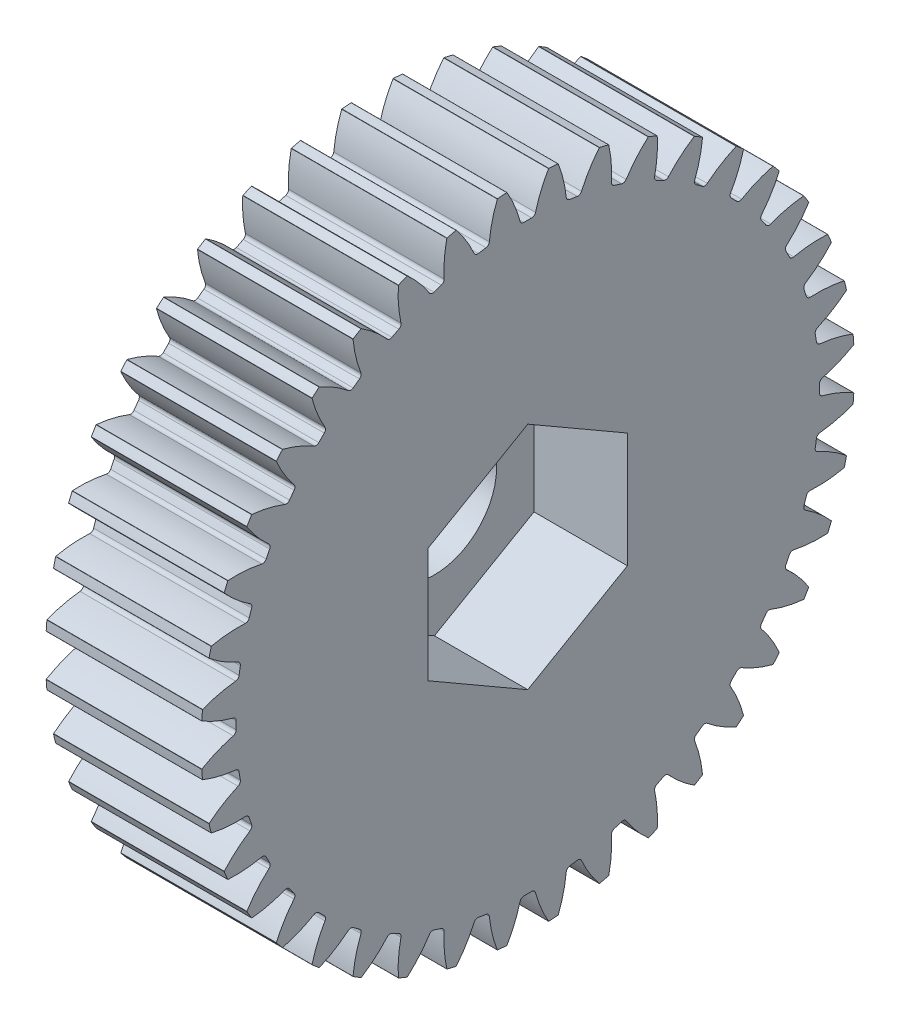
SolidWorks part; units mm, degrees
ref_plane "Plane1" through (0, 0, 0) normal (0, 0, 1) x (1, 0, 0)
ref_plane "Plane2" through (0, 0, 0) normal (0, 1, 0) x (1, 0, 0)
ref_plane "Plane3" through (0, 0, 0) normal (1, 0, 0) x (0, 0, -1)
sketch "HoldingSke" plane through (0, 0, 0) normal (0, 1, 0) x (1, 0, 0)
  line L0 (0, 0) -> (0.766, -0.6428)
  line L1 (-15, 0) -> (100, 0) construction
  line L2 (0, 0) -> (-2.1039, 2.3779)
  line L3 (0, 0) -> (-11.863, 4.5341)
  line L4 (0, 0) -> (6.6156, 5.5511)
  line L5 (0, 0) -> (-46.8476, -17.4728)
  line L6 (0, 0) -> (-11.6055, -7.8303)
  line L7 (-2.1039, 2.3779) -> (8.6586, 51.2059)
  line L8 (-76.2, 54.61) -> (-75.5, 54.61)
  line L9 (-71.009, 38.7566) -> (-53.1078, 45.2721)
  line L10 (-76.2, 71.12) -> (104.1128, 71.12)
  line L11 (0, 0) -> (-14, 0)
  line L12 (-76.2, 101.6) -> (-76.162, 101.6)
  line L13 (24.9733, 27.94) -> (52.9518, 28.4284)
  line L14 (24.9733, 27.94) -> (24.9743, 27.94)
  line L15 (24.9733, 27.94) -> (100.4006, 29.5858)
  line L16 (-63.627, -1) -> (-12.827, -1)
  circle A0 centre (0, 0) radius 2
  circle A1 centre (0, 0) radius 18.749
  circle A2 centre (0, 0) radius 37.5
  circle A3 centre (0, 0) radius 2
  dimension "MHD" = 37.498
  dimension "Hub_dia" = 75
  dimension "Bore" = 4
  dimension "MBD" = 4
  dimension "Num_teeth" = 40
  dimension "Pitch" = 1
  dimension "Overall_len" = 50
  dimension "Show_teeth" = 40
  dimension "Thickness" = 14
  dimension "OAL" = 50.0001
  dimension "T_dim" = 0.7
  dimension "Ap" = 20
  dimension "H" = 19.05
  dimension "Pitch_radius" = 180.3128
  dimension "Width" = 14
  dimension "Backlash" = 0.038
  dimension "Addendum_fac" = 1
  dimension "Dedendum_fac" = 1.25
  dimension "Clearance_fac" = 0.25
  dimension "Dedendum_add" = 0.001
  dimension "Module" = 1
sketch "BasProSke" plane through (0, 0, 0) normal (0, 1, 0) x (1, 0, 0)
  line L0 (-10, 0) -> (60, 0) construction
  line L1 (0, 0) -> (0, 21)
  line L2 (0, 0) -> (14, 0)
  line L3 (14, 0) -> (14, 21)
  line L4 (14, 21) -> (0, 21)
  dimension "Thickness" = 14
  dimension "Diameter" = 42
revolve "Base-Revolve" add sketch "BasProSke" angle 360 about L0
sketch "TooCutSke" plane through (0, 0, 0) normal (1, 0, 0) x (0, 0, -1)
  line L1 (0, 0) -> (0, 107) construction
  line L2 (0, 0) -> (-0.8517, 19.9819) construction
  line L3 (0, 0) -> (-3.1363, 39.8509) construction
  line L4 (-0.8517, 19.9819) -> (-1.5682, 19.9255) construction
  arc A0 (0.4487, 18.7436) -> (-0.4487, 18.7436) centre (0, 0) ccw
  arc A1 (1.3547, 20.9817) -> (-1.3547, 20.9817) centre (0, 0) ccw
  circle A2 centre (0, 0) radius 20 construction
  circle A3 centre (0, 0) radius 18.7939 construction
  arc A4 (-0.4487, 18.7436) -> (-1.3547, 20.9817) centre (-8.2322, 16.895) ccw
  arc A5 (1.3547, 20.9817) -> (0.4487, 18.7436) centre (8.2322, 16.895) ccw
  dimension "Root_dia" = 37.498
  dimension "Overcut_dia" = 42.0508
  dimension "Pitch_dia" = 40
  dimension "Base_dia" = 37.5877
  dimension "Flank_rad" = 8
  dimension "Half_ang" = 4.5
  dimension "Half_CT" = 0.7187
extrude "ToothCut" cut sketch "TooCutSke" along normal through all
fillet "Breaks" radius 0.02 2 edges at (7, 20.9572, -1.3402) (7, 20.9572, 1.3402) tangent propagation no
fillet "RootFillets" radius 0.251 2 edges at (7, 18.7436, -0.4487) (7, 18.7436, 0.4487)
pattern_circular "TeethCuts" count 40 every 9 about axis through (-10, 0, 0) along (1, 0, 0) of "ToothCut", "RootFillets", "Breaks"
sketch "HubNeaOneSke" plane through (0, 0, 0) normal (-1, 0, 0) x (0, 0, 1)
  circle A0 centre (0, 0) radius 18.749
  dimension "Diameter" = 37.498
extrude "HubNearOne" [suppressed] add sketch "HubNeaOneSke" along normal blind 36.0001
sketch "HubNeaBotSke" plane through (0, 0, 0) normal (-1, 0, 0) x (0, 0, 1)
  circle A0 centre (0, 0) radius 18.749
  dimension "Diameter" = 37.498
extrude "HubNearBoth" [suppressed] add sketch "HubNeaBotSke" along normal blind 18
ref_plane "FarPln" through (14, 0, 0) normal (1, 0, 0) x (0, 0, -1)
sketch "HubFarSke" plane through (14, 0, 0) normal (1, 0, 0) x (0, 0, -1)
  circle A0 centre (0, 0) radius 18.749
  dimension "Diameter" = 37.498
extrude "HubFar" [suppressed] add sketch "HubFarSke" along normal blind 18
sketch "BorSke" plane through (0, 0, 0) normal (1, 0, 0) x (0, 0, -1)
  circle A0 centre (0, 0) radius 2
extrude "Bore" cut sketch "BorSke" along normal mid plane 100.0001
sketch "KeySke" plane through (0, 0, 0) normal (1, 0, 0) x (0, 0, -1)
  line L0 (-0.8, 0) -> (-0.8, 2.7)
  line L1 (-0.8, 2.7) -> (0.8, 2.7)
  line L2 (0.8, 2.7) -> (0.8, 0)
  line L3 (0, 0) -> (0, 34) construction
  line L4 (-0.8, 0) -> (0.8, 0)
  dimension "Offset" = 2.7
  dimension "Width" = 1.6
extrude "Keyway" [suppressed] cut sketch "KeySke" along normal mid plane 100.0001
pattern_circular "Keyway2" [suppressed] count 2 every 90 about axis through (-10, 0, 0) along (1, 0, 0)
sketch "Sketch1" plane through (14, 0, 0) normal (1, 0, 0) x (0, 0, -1)
  line L1 (0, 7.3901) -> (-6.4, 3.695)
  line L2 (-6.4, 3.695) -> (-6.4, -3.695)
  line L3 (-6.4, -3.695) -> (0, -7.3901)
  line L4 (0, -7.3901) -> (6.4, -3.695)
  line L5 (6.4, -3.695) -> (6.4, 3.695)
  line L6 (6.4, 3.695) -> (0, 7.3901)
  circle A0 centre (0, 0) radius 7.3901
  circle A2 centre (0, 0) radius 6.4 construction
  circle A3 centre (0, 0) radius 4
  dimension "D1" = 8
  dimension "D2" = 12.8
extrude "Cut-Extrude1" cut sketch "Sketch1" against normal blind 6 contours L1 L2 L3 L4 L5 L6
extrude "Cut-Extrude2" cut sketch "Sketch1<7>" against normal through all contours A3 region at (14, 0, 0)
sketch "Sketch1<7>" plane through (14, 0, 0) normal (1, 0, 0) x (0, 0, -1) same geometry as "Sketch1"
sketch "Sketch2" plane through (0, 0, 0) normal (-1, 0, 0) x (0, 0, 1)
  circle A0 centre (0, 0) radius 6.5
  circle A1 centre (0, 0) radius 4
  dimension "D1" = 13
  dimension "D2" = 8
extrude "Boss-Extrude1" add sketch "Sketch2" along normal blind 3.8
sketch "Sketch3" plane through (8, 0, 0) normal (1, 0, 0) x (0, 0, -1)
  line L1 (4, 4) -> (-4, 4)
  line L2 (4, 4) -> (4, -4)
  line L3 (4, -4) -> (-4, -4)
  line L4 (-4, 4) -> (-4, -4)
  line L6 (5.5, 5.5) -> (5.5, -5.5)
  line L7 (5.5, -5.5) -> (-5.5, -5.5)
  line L8 (-5.5, 5.5) -> (-5.5, -5.5)
  line L9 (5.5, 5.5) -> (-5.5, 5.5)
  line L10 (5.5, 4) -> (5.8718, 4)
  line L11 (6.4, 3.695) -> (0, 7.3901) construction
  line L12 (5.5, -4) -> (5.8718, -4)
  line L13 (0, -7.3901) -> (6.4, -3.695) construction
  line L14 (-5.5, -4) -> (-5.8718, -4)
  line L15 (-6.4, -3.695) -> (0, -7.3901) construction
  line L16 (-5.5, 4) -> (-5.8718, 4)
  line L17 (0, 7.3901) -> (-6.4, 3.695) construction
  circle A0 centre (0, 0) radius 4 construction
  line M10 (6.4, 3.695) -> (0, 7.3901)
  line M11 (0, 7.3901) -> (-6.4, 3.695)
  line M13 (-6.4, -3.695) -> (0, -7.3901)
  line M14 (0, -7.3901) -> (6.4, -3.695)
  dimension "D1" = 1.5
extrude "Boss-Extrude2" [suppressed] add sketch "Sketch3" along normal blind 0.3 contours L9 L8 L7 L6 L4 L1 L2 L3 M10 M11 M13 M14 | L12 L6 M14 | L6 L10 M10 | L16 L8 M11 | L8 L14 M13
sketch "Sketch4" plane through (0, 0, 0) normal (-1, 0, 0) x (0, 0, 1)
  circle A324 centre (0, 0) radius 6.5
  circle A325 centre (0, 0) radius 6.5
  arc A644 (-2.6854, 18.5557) -> (-3.18, 18.4773) centre (0, 0) ccw
  arc A645 (-3.4523, 18.6235) -> (-3.18, 18.4773) centre (-3.2226, 18.7247) ccw
  arc A646 (-3.4523, 18.6235) -> (-4.5943, 20.48) centre (-10.7738, 15.3992) ccw
  arc A647 (-4.5943, 20.48) -> (-4.6142, 20.4868) centre (-4.6098, 20.4673) ccw
  arc A648 (-4.6142, 20.4868) -> (-5.1896, 20.3487) centre (0, 0) ccw
  arc A649 (-5.1896, 20.3487) -> (-5.2042, 20.3336) centre (-5.1846, 20.3293) ccw
  arc A650 (-5.2042, 20.3336) -> (-5.3789, 18.161) centre (2.6084, 18.612) ccw
  arc A651 (-5.5551, 17.9071) -> (-5.3789, 18.161) centre (-5.6295, 18.1469) ccw
  arc A652 (-5.5551, 17.9071) -> (-6.0314, 17.7524) centre (0, 0) ccw
  arc A653 (-6.3232, 17.8542) -> (-6.0314, 17.7524) centre (-6.1121, 17.9901) ccw
  arc A654 (-6.3232, 17.8542) -> (-7.7415, 19.5091) centre (-13.0501, 13.5242) ccw
  arc A655 (-7.7415, 19.5091) -> (-7.7622, 19.5128) centre (-7.7548, 19.4942) ccw
  arc A656 (-7.7622, 19.5128) -> (-8.3089, 19.2863) centre (0, 0) ccw
  arc A657 (-8.3089, 19.2863) -> (-8.321, 19.2691) centre (-8.301, 19.268) ccw
  arc A658 (-8.321, 19.2691) -> (-8.1537, 17.096) centre (-0.3353, 18.7909) ccw
  arc A659 (-8.288, 16.8177) -> (-8.1537, 17.096) centre (-8.399, 17.0428) ccw
  arc A660 (-8.288, 16.8177) -> (-8.7342, 16.5903) centre (0, 0) ccw
  arc A661 (-9.0383, 16.6452) -> (-8.7342, 16.5903) centre (-8.8511, 16.8124) ccw
  arc A662 (-9.0383, 16.6452) -> (-10.6981, 18.0579) centre (-15.0051, 11.3162) ccw
  arc A663 (-10.6981, 18.0579) -> (-10.7191, 18.0583) centre (-10.7089, 18.0411) ccw
  arc A664 (-10.7191, 18.0583) -> (-11.2237, 17.7491) centre (0, 0) ccw
  arc A665 (-11.2237, 17.7491) -> (-11.2329, 17.7302) centre (-11.213, 17.7322) ccw
  arc A666 (-11.2329, 17.7302) -> (-10.7277, 15.61) centre (-3.2707, 18.5071) ccw
  arc A667 (-10.8168, 15.3141) -> (-10.7277, 15.61) centre (-10.9616, 15.5191) ccw
  arc A668 (-10.8168, 15.3141) -> (-11.222, 15.0197) centre (0, 0) ccw
  arc A669 (-11.5309, 15.0264) -> (-11.222, 15.0197) centre (-11.3722, 15.2208) ccw
  arc A670 (-11.5309, 15.0264) -> (-13.3913, 16.162) centre (-16.5906, 8.8296) ccw
  arc A671 (-13.3913, 16.162) -> (-13.4121, 16.1591) centre (-13.3993, 16.1437) ccw
  arc A672 (-13.4121, 16.1591) -> (-13.862, 15.7748) centre (0, 0) ccw
  arc A673 (-13.862, 15.7748) -> (-13.8682, 15.7547) centre (-13.8488, 15.7598) ccw
  arc A674 (-13.8682, 15.7547) -> (-13.0375, 13.7396) centre (-6.1256, 17.7676) ccw
  arc A675 (-13.0793, 13.4334) -> (-13.0375, 13.7396) centre (-13.2544, 13.6133) ccw
  arc A676 (-13.0793, 13.4334) -> (-13.4334, 13.0793) centre (0, 0) ccw
  arc A677 (-13.7396, 13.0375) -> (-13.4334, 13.0793) centre (-13.6133, 13.2544) ccw
  arc A678 (-13.7396, 13.0375) -> (-15.7547, 13.8682) centre (-17.7676, 6.1256) ccw
  arc A679 (-15.7547, 13.8682) -> (-15.7748, 13.862) centre (-15.7598, 13.8488) ccw
  arc A680 (-15.7748, 13.862) -> (-16.1591, 13.4121) centre (0, 0) ccw
  arc A681 (-16.1591, 13.4121) -> (-16.162, 13.3913) centre (-16.1437, 13.3993) ccw
  arc A682 (-16.162, 13.3913) -> (-15.0264, 11.5309) centre (-8.8296, 16.5906) ccw
  arc A683 (-15.0197, 11.222) -> (-15.0264, 11.5309) centre (-15.2208, 11.3722) ccw
  arc A684 (-15.0197, 11.222) -> (-15.3141, 10.8168) centre (0, 0) ccw
  arc A685 (-15.61, 10.7277) -> (-15.3141, 10.8168) centre (-15.5191, 10.9616) ccw
  arc A686 (-15.61, 10.7277) -> (-17.7302, 11.2329) centre (-18.5071, 3.2707) ccw
  arc A687 (-17.7302, 11.2329) -> (-17.7491, 11.2237) centre (-17.7322, 11.213) ccw
  arc A688 (-17.7491, 11.2237) -> (-18.0583, 10.7191) centre (0, 0) ccw
  arc A689 (-18.0583, 10.7191) -> (-18.0579, 10.6981) centre (-18.0411, 10.7089) ccw
  arc A690 (-18.0579, 10.6981) -> (-16.6452, 9.0383) centre (-11.3162, 15.0051) ccw
  arc A691 (-16.5903, 8.7342) -> (-16.6452, 9.0383) centre (-16.8124, 8.8511) ccw
  arc A692 (-16.5903, 8.7342) -> (-16.8177, 8.288) centre (0, 0) ccw
  arc A693 (-17.096, 8.1537) -> (-16.8177, 8.288) centre (-17.0428, 8.399) ccw
  arc A694 (-17.096, 8.1537) -> (-19.2691, 8.321) centre (-18.7909, 0.3353) ccw
  arc A695 (-19.2691, 8.321) -> (-19.2863, 8.3089) centre (-19.268, 8.301) ccw
  arc A696 (-19.2863, 8.3089) -> (-19.5128, 7.7622) centre (0, 0) ccw
  arc A697 (-19.5128, 7.7622) -> (-19.5091, 7.7415) centre (-19.4942, 7.7548) ccw
  arc A698 (-19.5091, 7.7415) -> (-17.8542, 6.3232) centre (-13.5242, 13.0501) ccw
  arc A699 (-17.7524, 6.0314) -> (-17.8542, 6.3232) centre (-17.9901, 6.1121) ccw
  arc A700 (-17.7524, 6.0314) -> (-17.9071, 5.5551) centre (0, 0) ccw
  arc A701 (-18.161, 5.3789) -> (-17.9071, 5.5551) centre (-18.1469, 5.6295) ccw
  arc A702 (-18.161, 5.3789) -> (-20.3336, 5.2042) centre (-18.612, -2.6084) ccw
  arc A703 (-20.3336, 5.2042) -> (-20.3487, 5.1896) centre (-20.3293, 5.1846) ccw
  arc A704 (-20.3487, 5.1896) -> (-20.4868, 4.6142) centre (0, 0) ccw
  arc A705 (-20.4868, 4.6142) -> (-20.48, 4.5943) centre (-20.4673, 4.6098) ccw
  arc A706 (-20.48, 4.5943) -> (-18.6235, 3.4523) centre (-15.3992, 10.7738) ccw
  arc A707 (-18.4773, 3.18) -> (-18.6235, 3.4523) centre (-18.7247, 3.2226) ccw
  arc A708 (-18.4773, 3.18) -> (-18.5557, 2.6854) centre (0, 0) ccw
  arc A709 (-18.7789, 2.4716) -> (-18.5557, 2.6854) centre (-18.8041, 2.7214) ccw
  arc A710 (-18.7789, 2.4716) -> (-20.8974, 1.9592) centre (-17.9748, -5.4878) ccw
  arc A711 (-20.8974, 1.9592) -> (-20.91, 1.9424) centre (-20.8901, 1.9406) ccw
  arc A712 (-20.91, 1.9424) -> (-20.9564, 1.3525) centre (0, 0) ccw
  arc A713 (-20.9564, 1.3525) -> (-20.9466, 1.334) centre (-20.9364, 1.3512) ccw
  arc A714 (-20.9466, 1.334) -> (-18.9343, 0.4964) centre (-16.895, 8.2322) ccw
  arc A715 (-18.7473, 0.2504) -> (-18.9343, 0.4964) centre (-18.9983, 0.2537) ccw
  arc A716 (-18.7473, 0.2504) -> (-18.7473, -0.2504) centre (0, 0) ccw
  arc A717 (-18.9343, -0.4964) -> (-18.7473, -0.2504) centre (-18.9983, -0.2537) ccw
  arc A718 (-18.9343, -0.4964) -> (-20.9466, -1.334) centre (-16.895, -8.2322) ccw
  arc A719 (-20.9466, -1.334) -> (-20.9564, -1.3525) centre (-20.9364, -1.3512) ccw
  arc A720 (-20.9564, -1.3525) -> (-20.91, -1.9424) centre (0, 0) ccw
  arc A721 (-20.91, -1.9424) -> (-20.8974, -1.9592) centre (-20.8901, -1.9406) ccw
  arc A722 (-20.8974, -1.9592) -> (-18.7789, -2.4716) centre (-17.9748, 5.4878) ccw
  arc A723 (-18.5557, -2.6854) -> (-18.7789, -2.4716) centre (-18.8041, -2.7214) ccw
  arc A724 (-18.5557, -2.6854) -> (-18.4773, -3.18) centre (0, 0) ccw
  arc A725 (-18.6235, -3.4523) -> (-18.4773, -3.18) centre (-18.7247, -3.2226) ccw
  arc A726 (-18.6235, -3.4523) -> (-20.48, -4.5943) centre (-15.3992, -10.7738) ccw
  arc A727 (-20.48, -4.5943) -> (-20.4868, -4.6142) centre (-20.4673, -4.6098) ccw
  arc A728 (-20.4868, -4.6142) -> (-20.3487, -5.1896) centre (0, 0) ccw
  arc A729 (-20.3487, -5.1896) -> (-20.3336, -5.2042) centre (-20.3293, -5.1846) ccw
  arc A730 (-20.3336, -5.2042) -> (-18.161, -5.3789) centre (-18.612, 2.6084) ccw
  arc A731 (-17.9071, -5.5551) -> (-18.161, -5.3789) centre (-18.1469, -5.6295) ccw
  arc A732 (-17.9071, -5.5551) -> (-17.7524, -6.0314) centre (0, 0) ccw
  arc A733 (-17.8542, -6.3232) -> (-17.7524, -6.0314) centre (-17.9901, -6.1121) ccw
  arc A734 (-17.8542, -6.3232) -> (-19.5091, -7.7415) centre (-13.5242, -13.0501) ccw
  arc A735 (-19.5091, -7.7415) -> (-19.5128, -7.7622) centre (-19.4942, -7.7548) ccw
  arc A736 (-19.5128, -7.7622) -> (-19.2863, -8.3089) centre (0, 0) ccw
  arc A737 (-19.2863, -8.3089) -> (-19.2691, -8.321) centre (-19.268, -8.301) ccw
  arc A738 (-19.2691, -8.321) -> (-17.096, -8.1537) centre (-18.7909, -0.3353) ccw
  arc A739 (-16.8177, -8.288) -> (-17.096, -8.1537) centre (-17.0428, -8.399) ccw
  arc A740 (-16.8177, -8.288) -> (-16.5903, -8.7342) centre (0, 0) ccw
  arc A741 (-16.6452, -9.0383) -> (-16.5903, -8.7342) centre (-16.8124, -8.8511) ccw
  arc A742 (-16.6452, -9.0383) -> (-18.0579, -10.6981) centre (-11.3162, -15.0051) ccw
  arc A743 (-18.0579, -10.6981) -> (-18.0583, -10.7191) centre (-18.0411, -10.7089) ccw
  arc A744 (-18.0583, -10.7191) -> (-17.7491, -11.2237) centre (0, 0) ccw
  arc A745 (-17.7491, -11.2237) -> (-17.7302, -11.2329) centre (-17.7322, -11.213) ccw
  arc A746 (-17.7302, -11.2329) -> (-15.61, -10.7277) centre (-18.5071, -3.2707) ccw
  arc A747 (-15.3141, -10.8168) -> (-15.61, -10.7277) centre (-15.5191, -10.9616) ccw
  arc A748 (-15.3141, -10.8168) -> (-15.0197, -11.222) centre (0, 0) ccw
  arc A749 (-15.0264, -11.5309) -> (-15.0197, -11.222) centre (-15.2208, -11.3722) ccw
  arc A750 (-15.0264, -11.5309) -> (-16.162, -13.3913) centre (-8.8296, -16.5906) ccw
  arc A751 (-16.162, -13.3913) -> (-16.1591, -13.4121) centre (-16.1437, -13.3993) ccw
  arc A752 (-16.1591, -13.4121) -> (-15.7748, -13.862) centre (0, 0) ccw
  arc A753 (-15.7748, -13.862) -> (-15.7547, -13.8682) centre (-15.7598, -13.8488) ccw
  arc A754 (-15.7547, -13.8682) -> (-13.7396, -13.0375) centre (-17.7676, -6.1256) ccw
  arc A755 (-13.4334, -13.0793) -> (-13.7396, -13.0375) centre (-13.6133, -13.2544) ccw
  arc A756 (-13.4334, -13.0793) -> (-13.0793, -13.4334) centre (0, 0) ccw
  arc A757 (-13.0375, -13.7396) -> (-13.0793, -13.4334) centre (-13.2544, -13.6133) ccw
  arc A758 (-13.0375, -13.7396) -> (-13.8682, -15.7547) centre (-6.1256, -17.7676) ccw
  arc A759 (-13.8682, -15.7547) -> (-13.862, -15.7748) centre (-13.8488, -15.7598) ccw
  arc A760 (-13.862, -15.7748) -> (-13.4121, -16.1591) centre (0, 0) ccw
  arc A761 (-13.4121, -16.1591) -> (-13.3913, -16.162) centre (-13.3993, -16.1437) ccw
  arc A762 (-13.3913, -16.162) -> (-11.5309, -15.0264) centre (-16.5906, -8.8296) ccw
  arc A763 (-11.222, -15.0197) -> (-11.5309, -15.0264) centre (-11.3722, -15.2208) ccw
  arc A764 (-11.222, -15.0197) -> (-10.8168, -15.3141) centre (0, 0) ccw
  arc A765 (-10.7277, -15.61) -> (-10.8168, -15.3141) centre (-10.9616, -15.5191) ccw
  arc A766 (-10.7277, -15.61) -> (-11.2329, -17.7302) centre (-3.2707, -18.5071) ccw
  arc A767 (-11.2329, -17.7302) -> (-11.2237, -17.7491) centre (-11.213, -17.7322) ccw
  arc A768 (-11.2237, -17.7491) -> (-10.7191, -18.0583) centre (0, 0) ccw
  arc A769 (-10.7191, -18.0583) -> (-10.6981, -18.0579) centre (-10.7089, -18.0411) ccw
  arc A770 (-10.6981, -18.0579) -> (-9.0383, -16.6452) centre (-15.0051, -11.3162) ccw
  arc A771 (-8.7342, -16.5903) -> (-9.0383, -16.6452) centre (-8.8511, -16.8124) ccw
  arc A772 (-8.7342, -16.5903) -> (-8.288, -16.8177) centre (0, 0) ccw
  arc A773 (-8.1537, -17.096) -> (-8.288, -16.8177) centre (-8.399, -17.0428) ccw
  arc A774 (-8.1537, -17.096) -> (-8.321, -19.2691) centre (-0.3353, -18.7909) ccw
  arc A775 (-8.321, -19.2691) -> (-8.3089, -19.2863) centre (-8.301, -19.268) ccw
  arc A776 (-8.3089, -19.2863) -> (-7.7622, -19.5128) centre (0, 0) ccw
  arc A777 (-7.7622, -19.5128) -> (-7.7415, -19.5091) centre (-7.7548, -19.4942) ccw
  arc A778 (-7.7415, -19.5091) -> (-6.3232, -17.8542) centre (-13.0501, -13.5242) ccw
  arc A779 (-6.0314, -17.7524) -> (-6.3232, -17.8542) centre (-6.1121, -17.9901) ccw
  arc A780 (-6.0314, -17.7524) -> (-5.5551, -17.9071) centre (0, 0) ccw
  arc A781 (-5.3789, -18.161) -> (-5.5551, -17.9071) centre (-5.6295, -18.1469) ccw
  arc A782 (-5.3789, -18.161) -> (-5.2042, -20.3336) centre (2.6084, -18.612) ccw
  arc A783 (-5.2042, -20.3336) -> (-5.1896, -20.3487) centre (-5.1846, -20.3293) ccw
  arc A784 (-5.1896, -20.3487) -> (-4.6142, -20.4868) centre (0, 0) ccw
  arc A785 (-4.6142, -20.4868) -> (-4.5943, -20.48) centre (-4.6098, -20.4673) ccw
  arc A786 (-4.5943, -20.48) -> (-3.4523, -18.6235) centre (-10.7738, -15.3992) ccw
  arc A787 (-3.18, -18.4773) -> (-3.4523, -18.6235) centre (-3.2226, -18.7247) ccw
  arc A788 (-3.18, -18.4773) -> (-2.6854, -18.5557) centre (0, 0) ccw
  arc A789 (-2.4716, -18.7789) -> (-2.6854, -18.5557) centre (-2.7214, -18.8041) ccw
  arc A790 (-2.4716, -18.7789) -> (-1.9592, -20.8974) centre (5.4878, -17.9748) ccw
  arc A791 (-1.9592, -20.8974) -> (-1.9424, -20.91) centre (-1.9406, -20.8901) ccw
  arc A792 (-1.9424, -20.91) -> (-1.3525, -20.9564) centre (0, 0) ccw
  arc A793 (-1.3525, -20.9564) -> (-1.334, -20.9466) centre (-1.3512, -20.9364) ccw
  arc A794 (-1.334, -20.9466) -> (-0.4964, -18.9343) centre (-8.2322, -16.895) ccw
  arc A795 (-0.2504, -18.7473) -> (-0.4964, -18.9343) centre (-0.2537, -18.9983) ccw
  arc A796 (-0.2504, -18.7473) -> (0.2504, -18.7473) centre (0, 0) ccw
  arc A797 (0.4964, -18.9343) -> (0.2504, -18.7473) centre (0.2537, -18.9983) ccw
  arc A798 (0.4964, -18.9343) -> (1.334, -20.9466) centre (8.2322, -16.895) ccw
  arc A799 (1.334, -20.9466) -> (1.3525, -20.9564) centre (1.3512, -20.9364) ccw
  arc A800 (1.3525, -20.9564) -> (1.9424, -20.91) centre (0, 0) ccw
  arc A801 (1.9424, -20.91) -> (1.9592, -20.8974) centre (1.9406, -20.8901) ccw
  arc A802 (1.9592, -20.8974) -> (2.4716, -18.7789) centre (-5.4878, -17.9748) ccw
  arc A803 (2.6854, -18.5557) -> (2.4716, -18.7789) centre (2.7214, -18.8041) ccw
  arc A804 (2.6854, -18.5557) -> (3.18, -18.4773) centre (0, 0) ccw
  arc A805 (3.4523, -18.6235) -> (3.18, -18.4773) centre (3.2226, -18.7247) ccw
  arc A806 (3.4523, -18.6235) -> (4.5943, -20.48) centre (10.7738, -15.3992) ccw
  arc A807 (4.5943, -20.48) -> (4.6142, -20.4868) centre (4.6098, -20.4673) ccw
  arc A808 (4.6142, -20.4868) -> (5.1896, -20.3487) centre (0, 0) ccw
  arc A809 (5.1896, -20.3487) -> (5.2042, -20.3336) centre (5.1846, -20.3293) ccw
  arc A810 (5.2042, -20.3336) -> (5.3789, -18.161) centre (-2.6084, -18.612) ccw
  arc A811 (5.5551, -17.9071) -> (5.3789, -18.161) centre (5.6295, -18.1469) ccw
  arc A812 (5.5551, -17.9071) -> (6.0314, -17.7524) centre (0, 0) ccw
  arc A813 (6.3232, -17.8542) -> (6.0314, -17.7524) centre (6.1121, -17.9901) ccw
  arc A814 (6.3232, -17.8542) -> (7.7415, -19.5091) centre (13.0501, -13.5242) ccw
  arc A815 (7.7415, -19.5091) -> (7.7622, -19.5128) centre (7.7548, -19.4942) ccw
  arc A816 (7.7622, -19.5128) -> (8.3089, -19.2863) centre (0, 0) ccw
  arc A817 (8.3089, -19.2863) -> (8.321, -19.2691) centre (8.301, -19.268) ccw
  arc A818 (8.321, -19.2691) -> (8.1537, -17.096) centre (0.3353, -18.7909) ccw
  arc A819 (8.288, -16.8177) -> (8.1537, -17.096) centre (8.399, -17.0428) ccw
  arc A820 (8.288, -16.8177) -> (8.7342, -16.5903) centre (0, 0) ccw
  arc A821 (9.0383, -16.6452) -> (8.7342, -16.5903) centre (8.8511, -16.8124) ccw
  arc A822 (9.0383, -16.6452) -> (10.6981, -18.0579) centre (15.0051, -11.3162) ccw
  arc A823 (10.6981, -18.0579) -> (10.7191, -18.0583) centre (10.7089, -18.0411) ccw
  arc A824 (10.7191, -18.0583) -> (11.2237, -17.7491) centre (0, 0) ccw
  arc A825 (11.2237, -17.7491) -> (11.2329, -17.7302) centre (11.213, -17.7322) ccw
  arc A826 (11.2329, -17.7302) -> (10.7277, -15.61) centre (3.2707, -18.5071) ccw
  arc A827 (10.8168, -15.3141) -> (10.7277, -15.61) centre (10.9616, -15.5191) ccw
  arc A828 (10.8168, -15.3141) -> (11.222, -15.0197) centre (0, 0) ccw
  arc A829 (11.5309, -15.0264) -> (11.222, -15.0197) centre (11.3722, -15.2208) ccw
  arc A830 (11.5309, -15.0264) -> (13.3913, -16.162) centre (16.5906, -8.8296) ccw
  arc A831 (13.3913, -16.162) -> (13.4121, -16.1591) centre (13.3993, -16.1437) ccw
  arc A832 (13.4121, -16.1591) -> (13.862, -15.7748) centre (0, 0) ccw
  arc A833 (13.862, -15.7748) -> (13.8682, -15.7547) centre (13.8488, -15.7598) ccw
  arc A834 (13.8682, -15.7547) -> (13.0375, -13.7396) centre (6.1256, -17.7676) ccw
  arc A835 (13.0793, -13.4334) -> (13.0375, -13.7396) centre (13.2544, -13.6133) ccw
  arc A836 (13.0793, -13.4334) -> (13.4334, -13.0793) centre (0, 0) ccw
  arc A837 (13.7396, -13.0375) -> (13.4334, -13.0793) centre (13.6133, -13.2544) ccw
  arc A838 (13.7396, -13.0375) -> (15.7547, -13.8682) centre (17.7676, -6.1256) ccw
  arc A839 (15.7547, -13.8682) -> (15.7748, -13.862) centre (15.7598, -13.8488) ccw
  arc A840 (15.7748, -13.862) -> (16.1591, -13.4121) centre (0, 0) ccw
  arc A841 (16.1591, -13.4121) -> (16.162, -13.3913) centre (16.1437, -13.3993) ccw
  arc A842 (16.162, -13.3913) -> (15.0264, -11.5309) centre (8.8296, -16.5906) ccw
  arc A843 (15.0197, -11.222) -> (15.0264, -11.5309) centre (15.2208, -11.3722) ccw
  arc A844 (15.0197, -11.222) -> (15.3141, -10.8168) centre (0, 0) ccw
  arc A845 (15.61, -10.7277) -> (15.3141, -10.8168) centre (15.5191, -10.9616) ccw
  arc A846 (15.61, -10.7277) -> (17.7302, -11.2329) centre (18.5071, -3.2707) ccw
  arc A847 (17.7302, -11.2329) -> (17.7491, -11.2237) centre (17.7322, -11.213) ccw
  arc A848 (17.7491, -11.2237) -> (18.0583, -10.7191) centre (0, 0) ccw
  arc A849 (18.0583, -10.7191) -> (18.0579, -10.6981) centre (18.0411, -10.7089) ccw
  arc A850 (18.0579, -10.6981) -> (16.6452, -9.0383) centre (11.3162, -15.0051) ccw
  arc A851 (16.5903, -8.7342) -> (16.6452, -9.0383) centre (16.8124, -8.8511) ccw
  arc A852 (16.5903, -8.7342) -> (16.8177, -8.288) centre (0, 0) ccw
  arc A853 (17.096, -8.1537) -> (16.8177, -8.288) centre (17.0428, -8.399) ccw
  arc A854 (17.096, -8.1537) -> (19.2691, -8.321) centre (18.7909, -0.3353) ccw
  arc A855 (19.2691, -8.321) -> (19.2863, -8.3089) centre (19.268, -8.301) ccw
  arc A856 (19.2863, -8.3089) -> (19.5128, -7.7622) centre (0, 0) ccw
  arc A857 (19.5128, -7.7622) -> (19.5091, -7.7415) centre (19.4942, -7.7548) ccw
  arc A858 (19.5091, -7.7415) -> (17.8542, -6.3232) centre (13.5242, -13.0501) ccw
  arc A859 (17.7524, -6.0314) -> (17.8542, -6.3232) centre (17.9901, -6.1121) ccw
  arc A860 (17.7524, -6.0314) -> (17.9071, -5.5551) centre (0, 0) ccw
  arc A861 (18.161, -5.3789) -> (17.9071, -5.5551) centre (18.1469, -5.6295) ccw
  arc A862 (18.161, -5.3789) -> (20.3336, -5.2042) centre (18.612, 2.6084) ccw
  arc A863 (20.3336, -5.2042) -> (20.3487, -5.1896) centre (20.3293, -5.1846) ccw
  arc A864 (20.3487, -5.1896) -> (20.4868, -4.6142) centre (0, 0) ccw
  arc A865 (20.4868, -4.6142) -> (20.48, -4.5943) centre (20.4673, -4.6098) ccw
  arc A866 (20.48, -4.5943) -> (18.6235, -3.4523) centre (15.3992, -10.7738) ccw
  arc A867 (18.4773, -3.18) -> (18.6235, -3.4523) centre (18.7247, -3.2226) ccw
  arc A868 (18.4773, -3.18) -> (18.5557, -2.6854) centre (0, 0) ccw
  arc A869 (18.7789, -2.4716) -> (18.5557, -2.6854) centre (18.8041, -2.7214) ccw
  arc A870 (18.7789, -2.4716) -> (20.8974, -1.9592) centre (17.9748, 5.4878) ccw
  arc A871 (20.8974, -1.9592) -> (20.91, -1.9424) centre (20.8901, -1.9406) ccw
  arc A872 (20.91, -1.9424) -> (20.9564, -1.3525) centre (0, 0) ccw
  arc A873 (20.9564, -1.3525) -> (20.9466, -1.334) centre (20.9364, -1.3512) ccw
  arc A874 (20.9466, -1.334) -> (18.9343, -0.4964) centre (16.895, -8.2322) ccw
  arc A875 (18.7473, -0.2504) -> (18.9343, -0.4964) centre (18.9983, -0.2537) ccw
  arc A876 (18.7473, -0.2504) -> (18.7473, 0.2504) centre (0, 0) ccw
  arc A877 (18.9343, 0.4964) -> (18.7473, 0.2504) centre (18.9983, 0.2537) ccw
  arc A878 (18.9343, 0.4964) -> (20.9466, 1.334) centre (16.895, 8.2322) ccw
  arc A879 (20.9466, 1.334) -> (20.9564, 1.3525) centre (20.9364, 1.3512) ccw
  arc A880 (20.9564, 1.3525) -> (20.91, 1.9424) centre (0, 0) ccw
  arc A881 (20.91, 1.9424) -> (20.8974, 1.9592) centre (20.8901, 1.9406) ccw
  arc A882 (20.8974, 1.9592) -> (18.7789, 2.4716) centre (17.9748, -5.4878) ccw
  arc A883 (18.5557, 2.6854) -> (18.7789, 2.4716) centre (18.8041, 2.7214) ccw
  arc A884 (18.5557, 2.6854) -> (18.4773, 3.18) centre (0, 0) ccw
  arc A885 (18.6235, 3.4523) -> (18.4773, 3.18) centre (18.7247, 3.2226) ccw
  arc A886 (18.6235, 3.4523) -> (20.48, 4.5943) centre (15.3992, 10.7738) ccw
  arc A887 (20.48, 4.5943) -> (20.4868, 4.6142) centre (20.4673, 4.6098) ccw
  arc A888 (20.4868, 4.6142) -> (20.3487, 5.1896) centre (0, 0) ccw
  arc A889 (20.3487, 5.1896) -> (20.3336, 5.2042) centre (20.3293, 5.1846) ccw
  arc A890 (20.3336, 5.2042) -> (18.161, 5.3789) centre (18.612, -2.6084) ccw
  arc A891 (17.9071, 5.5551) -> (18.161, 5.3789) centre (18.1469, 5.6295) ccw
  arc A892 (17.9071, 5.5551) -> (17.7524, 6.0314) centre (0, 0) ccw
  arc A893 (17.8542, 6.3232) -> (17.7524, 6.0314) centre (17.9901, 6.1121) ccw
  arc A894 (17.8542, 6.3232) -> (19.5091, 7.7415) centre (13.5242, 13.0501) ccw
  arc A895 (19.5091, 7.7415) -> (19.5128, 7.7622) centre (19.4942, 7.7548) ccw
  arc A896 (19.5128, 7.7622) -> (19.2863, 8.3089) centre (0, 0) ccw
  arc A897 (19.2863, 8.3089) -> (19.2691, 8.321) centre (19.268, 8.301) ccw
  arc A898 (19.2691, 8.321) -> (17.096, 8.1537) centre (18.7909, 0.3353) ccw
  arc A899 (16.8177, 8.288) -> (17.096, 8.1537) centre (17.0428, 8.399) ccw
  arc A900 (16.8177, 8.288) -> (16.5903, 8.7342) centre (0, 0) ccw
  arc A901 (16.6452, 9.0383) -> (16.5903, 8.7342) centre (16.8124, 8.8511) ccw
  arc A902 (16.6452, 9.0383) -> (18.0579, 10.6981) centre (11.3162, 15.0051) ccw
  arc A903 (18.0579, 10.6981) -> (18.0583, 10.7191) centre (18.0411, 10.7089) ccw
  arc A904 (18.0583, 10.7191) -> (17.7491, 11.2237) centre (0, 0) ccw
  arc A905 (17.7491, 11.2237) -> (17.7302, 11.2329) centre (17.7322, 11.213) ccw
  arc A906 (17.7302, 11.2329) -> (15.61, 10.7277) centre (18.5071, 3.2707) ccw
  arc A907 (15.3141, 10.8168) -> (15.61, 10.7277) centre (15.5191, 10.9616) ccw
  arc A908 (15.3141, 10.8168) -> (15.0197, 11.222) centre (0, 0) ccw
  arc A909 (15.0264, 11.5309) -> (15.0197, 11.222) centre (15.2208, 11.3722) ccw
  arc A910 (15.0264, 11.5309) -> (16.162, 13.3913) centre (8.8296, 16.5906) ccw
  arc A911 (16.162, 13.3913) -> (16.1591, 13.4121) centre (16.1437, 13.3993) ccw
  arc A912 (16.1591, 13.4121) -> (15.7748, 13.862) centre (0, 0) ccw
  arc A913 (15.7748, 13.862) -> (15.7547, 13.8682) centre (15.7598, 13.8488) ccw
  arc A914 (15.7547, 13.8682) -> (13.7396, 13.0375) centre (17.7676, 6.1256) ccw
  arc A915 (13.4334, 13.0793) -> (13.7396, 13.0375) centre (13.6133, 13.2544) ccw
  arc A916 (13.4334, 13.0793) -> (13.0793, 13.4334) centre (0, 0) ccw
  arc A917 (13.0375, 13.7396) -> (13.0793, 13.4334) centre (13.2544, 13.6133) ccw
  arc A918 (13.0375, 13.7396) -> (13.8682, 15.7547) centre (6.1256, 17.7676) ccw
  arc A919 (13.8682, 15.7547) -> (13.862, 15.7748) centre (13.8488, 15.7598) ccw
  arc A920 (13.862, 15.7748) -> (13.4121, 16.1591) centre (0, 0) ccw
  arc A921 (13.4121, 16.1591) -> (13.3913, 16.162) centre (13.3993, 16.1437) ccw
  arc A922 (13.3913, 16.162) -> (11.5309, 15.0264) centre (16.5906, 8.8296) ccw
  arc A923 (11.222, 15.0197) -> (11.5309, 15.0264) centre (11.3722, 15.2208) ccw
  arc A924 (11.222, 15.0197) -> (10.8168, 15.3141) centre (0, 0) ccw
  arc A925 (10.7277, 15.61) -> (10.8168, 15.3141) centre (10.9616, 15.5191) ccw
  arc A926 (10.7277, 15.61) -> (11.2329, 17.7302) centre (3.2707, 18.5071) ccw
  arc A927 (11.2329, 17.7302) -> (11.2237, 17.7491) centre (11.213, 17.7322) ccw
  arc A928 (11.2237, 17.7491) -> (10.7191, 18.0583) centre (0, 0) ccw
  arc A929 (10.7191, 18.0583) -> (10.6981, 18.0579) centre (10.7089, 18.0411) ccw
  arc A930 (10.6981, 18.0579) -> (9.0383, 16.6452) centre (15.0051, 11.3162) ccw
  arc A931 (8.7342, 16.5903) -> (9.0383, 16.6452) centre (8.8511, 16.8124) ccw
  arc A932 (8.7342, 16.5903) -> (8.288, 16.8177) centre (0, 0) ccw
  arc A933 (8.1537, 17.096) -> (8.288, 16.8177) centre (8.399, 17.0428) ccw
  arc A934 (8.1537, 17.096) -> (8.321, 19.2691) centre (0.3353, 18.7909) ccw
  arc A935 (8.321, 19.2691) -> (8.3089, 19.2863) centre (8.301, 19.268) ccw
  arc A936 (8.3089, 19.2863) -> (7.7622, 19.5128) centre (0, 0) ccw
  arc A937 (7.7622, 19.5128) -> (7.7415, 19.5091) centre (7.7548, 19.4942) ccw
  arc A938 (7.7415, 19.5091) -> (6.3232, 17.8542) centre (13.0501, 13.5242) ccw
  arc A939 (6.0314, 17.7524) -> (6.3232, 17.8542) centre (6.1121, 17.9901) ccw
  arc A940 (6.0314, 17.7524) -> (5.5551, 17.9071) centre (0, 0) ccw
  arc A941 (5.3789, 18.161) -> (5.5551, 17.9071) centre (5.6295, 18.1469) ccw
  arc A942 (5.3789, 18.161) -> (5.2042, 20.3336) centre (-2.6084, 18.612) ccw
  arc A943 (5.2042, 20.3336) -> (5.1896, 20.3487) centre (5.1846, 20.3293) ccw
  arc A944 (5.1896, 20.3487) -> (4.6142, 20.4868) centre (0, 0) ccw
  arc A945 (4.6142, 20.4868) -> (4.5943, 20.48) centre (4.6098, 20.4673) ccw
  arc A946 (4.5943, 20.48) -> (3.4523, 18.6235) centre (10.7738, 15.3992) ccw
  arc A947 (3.18, 18.4773) -> (3.4523, 18.6235) centre (3.2226, 18.7247) ccw
  arc A948 (3.18, 18.4773) -> (2.6854, 18.5557) centre (0, 0) ccw
  arc A949 (2.4716, 18.7789) -> (2.6854, 18.5557) centre (2.7214, 18.8041) ccw
  arc A950 (2.4716, 18.7789) -> (1.9592, 20.8974) centre (-5.4878, 17.9748) ccw
  arc A951 (1.9592, 20.8974) -> (1.9424, 20.91) centre (1.9406, 20.8901) ccw
  arc A952 (1.9424, 20.91) -> (1.3525, 20.9564) centre (0, 0) ccw
  arc A953 (1.3525, 20.9564) -> (1.334, 20.9466) centre (1.3512, 20.9364) ccw
  arc A954 (1.334, 20.9466) -> (0.4964, 18.9343) centre (8.2322, 16.895) ccw
  arc A955 (0.2504, 18.7473) -> (0.4964, 18.9343) centre (0.2537, 18.9983) ccw
  arc A956 (0.2504, 18.7473) -> (-0.2504, 18.7473) centre (0, 0) ccw
  arc A957 (-0.4964, 18.9343) -> (-0.2504, 18.7473) centre (-0.2537, 18.9983) ccw
  arc A958 (-0.4964, 18.9343) -> (-1.334, 20.9466) centre (-8.2322, 16.895) ccw
  arc A959 (-1.334, 20.9466) -> (-1.3525, 20.9564) centre (-1.3512, 20.9364) ccw
  arc A960 (-1.3525, 20.9564) -> (-1.9424, 20.91) centre (0, 0) ccw
  arc A961 (-1.9424, 20.91) -> (-1.9592, 20.8974) centre (-1.9406, 20.8901) ccw
  arc A962 (-1.9592, 20.8974) -> (-2.4716, 18.7789) centre (5.4878, 17.9748) ccw
  arc A963 (-2.6854, 18.5557) -> (-2.4716, 18.7789) centre (-2.7214, 18.8041) ccw
  arc A964 (-2.6854, 18.5557) -> (-3.18, 18.4773) centre (0, 0) ccw
  arc A965 (-3.4523, 18.6235) -> (-3.18, 18.4773) centre (-3.2226, 18.7247) ccw
  arc A966 (-3.4523, 18.6235) -> (-4.5943, 20.48) centre (-10.7738, 15.3992) ccw
  arc A967 (-4.5943, 20.48) -> (-4.6142, 20.4868) centre (-4.6098, 20.4673) ccw
  arc A968 (-4.6142, 20.4868) -> (-5.1896, 20.3487) centre (0, 0) ccw
  arc A969 (-5.1896, 20.3487) -> (-5.2042, 20.3336) centre (-5.1846, 20.3293) ccw
  arc A970 (-5.2042, 20.3336) -> (-5.3789, 18.161) centre (2.6084, 18.612) ccw
  arc A971 (-5.5551, 17.9071) -> (-5.3789, 18.161) centre (-5.6295, 18.1469) ccw
  arc A972 (-5.5551, 17.9071) -> (-6.0314, 17.7524) centre (0, 0) ccw
  arc A973 (-6.3232, 17.8542) -> (-6.0314, 17.7524) centre (-6.1121, 17.9901) ccw
  arc A974 (-6.3232, 17.8542) -> (-7.7415, 19.5091) centre (-13.0501, 13.5242) ccw
  arc A975 (-7.7415, 19.5091) -> (-7.7622, 19.5128) centre (-7.7548, 19.4942) ccw
  arc A976 (-7.7622, 19.5128) -> (-8.3089, 19.2863) centre (0, 0) ccw
  arc A977 (-8.3089, 19.2863) -> (-8.321, 19.2691) centre (-8.301, 19.268) ccw
  arc A978 (-8.321, 19.2691) -> (-8.1537, 17.096) centre (-0.3353, 18.7909) ccw
  arc A979 (-8.288, 16.8177) -> (-8.1537, 17.096) centre (-8.399, 17.0428) ccw
  arc A980 (-8.288, 16.8177) -> (-8.7342, 16.5903) centre (0, 0) ccw
  arc A981 (-9.0383, 16.6452) -> (-8.7342, 16.5903) centre (-8.8511, 16.8124) ccw
  arc A982 (-9.0383, 16.6452) -> (-10.6981, 18.0579) centre (-15.0051, 11.3162) ccw
  arc A983 (-10.6981, 18.0579) -> (-10.7191, 18.0583) centre (-10.7089, 18.0411) ccw
  arc A984 (-10.7191, 18.0583) -> (-11.2237, 17.7491) centre (0, 0) ccw
  arc A985 (-11.2237, 17.7491) -> (-11.2329, 17.7302) centre (-11.213, 17.7322) ccw
  arc A986 (-11.2329, 17.7302) -> (-10.7277, 15.61) centre (-3.2707, 18.5071) ccw
  arc A987 (-10.8168, 15.3141) -> (-10.7277, 15.61) centre (-10.9616, 15.5191) ccw
  arc A988 (-10.8168, 15.3141) -> (-11.222, 15.0197) centre (0, 0) ccw
  arc A989 (-11.5309, 15.0264) -> (-11.222, 15.0197) centre (-11.3722, 15.2208) ccw
  arc A990 (-11.5309, 15.0264) -> (-13.3913, 16.162) centre (-16.5906, 8.8296) ccw
  arc A991 (-13.3913, 16.162) -> (-13.4121, 16.1591) centre (-13.3993, 16.1437) ccw
  arc A992 (-13.4121, 16.1591) -> (-13.862, 15.7748) centre (0, 0) ccw
  arc A993 (-13.862, 15.7748) -> (-13.8682, 15.7547) centre (-13.8488, 15.7598) ccw
  arc A994 (-13.8682, 15.7547) -> (-13.0375, 13.7396) centre (-6.1256, 17.7676) ccw
  arc A995 (-13.0793, 13.4334) -> (-13.0375, 13.7396) centre (-13.2544, 13.6133) ccw
  arc A996 (-13.0793, 13.4334) -> (-13.4334, 13.0793) centre (0, 0) ccw
  arc A997 (-13.7396, 13.0375) -> (-13.4334, 13.0793) centre (-13.6133, 13.2544) ccw
  arc A998 (-13.7396, 13.0375) -> (-15.7547, 13.8682) centre (-17.7676, 6.1256) ccw
  arc A999 (-15.7547, 13.8682) -> (-15.7748, 13.862) centre (-15.7598, 13.8488) ccw
  arc A1000 (-15.7748, 13.862) -> (-16.1591, 13.4121) centre (0, 0) ccw
  arc A1001 (-16.1591, 13.4121) -> (-16.162, 13.3913) centre (-16.1437, 13.3993) ccw
  arc A1002 (-16.162, 13.3913) -> (-15.0264, 11.5309) centre (-8.8296, 16.5906) ccw
  arc A1003 (-15.0197, 11.222) -> (-15.0264, 11.5309) centre (-15.2208, 11.3722) ccw
  arc A1004 (-15.0197, 11.222) -> (-15.3141, 10.8168) centre (0, 0) ccw
  arc A1005 (-15.61, 10.7277) -> (-15.3141, 10.8168) centre (-15.5191, 10.9616) ccw
  arc A1006 (-15.61, 10.7277) -> (-17.7302, 11.2329) centre (-18.5071, 3.2707) ccw
  arc A1007 (-17.7302, 11.2329) -> (-17.7491, 11.2237) centre (-17.7322, 11.213) ccw
  arc A1008 (-17.7491, 11.2237) -> (-18.0583, 10.7191) centre (0, 0) ccw
  arc A1009 (-18.0583, 10.7191) -> (-18.0579, 10.6981) centre (-18.0411, 10.7089) ccw
  arc A1010 (-18.0579, 10.6981) -> (-16.6452, 9.0383) centre (-11.3162, 15.0051) ccw
  arc A1011 (-16.5903, 8.7342) -> (-16.6452, 9.0383) centre (-16.8124, 8.8511) ccw
  arc A1012 (-16.5903, 8.7342) -> (-16.8177, 8.288) centre (0, 0) ccw
  arc A1013 (-17.096, 8.1537) -> (-16.8177, 8.288) centre (-17.0428, 8.399) ccw
  arc A1014 (-17.096, 8.1537) -> (-19.2691, 8.321) centre (-18.7909, 0.3353) ccw
  arc A1015 (-19.2691, 8.321) -> (-19.2863, 8.3089) centre (-19.268, 8.301) ccw
  arc A1016 (-19.2863, 8.3089) -> (-19.5128, 7.7622) centre (0, 0) ccw
  arc A1017 (-19.5128, 7.7622) -> (-19.5091, 7.7415) centre (-19.4942, 7.7548) ccw
  arc A1018 (-19.5091, 7.7415) -> (-17.8542, 6.3232) centre (-13.5242, 13.0501) ccw
  arc A1019 (-17.7524, 6.0314) -> (-17.8542, 6.3232) centre (-17.9901, 6.1121) ccw
  arc A1020 (-17.7524, 6.0314) -> (-17.9071, 5.5551) centre (0, 0) ccw
  arc A1021 (-18.161, 5.3789) -> (-17.9071, 5.5551) centre (-18.1469, 5.6295) ccw
  arc A1022 (-18.161, 5.3789) -> (-20.3336, 5.2042) centre (-18.612, -2.6084) ccw
  arc A1023 (-20.3336, 5.2042) -> (-20.3487, 5.1896) centre (-20.3293, 5.1846) ccw
  arc A1024 (-20.3487, 5.1896) -> (-20.4868, 4.6142) centre (0, 0) ccw
  arc A1025 (-20.4868, 4.6142) -> (-20.48, 4.5943) centre (-20.4673, 4.6098) ccw
  arc A1026 (-20.48, 4.5943) -> (-18.6235, 3.4523) centre (-15.3992, 10.7738) ccw
  arc A1027 (-18.4773, 3.18) -> (-18.6235, 3.4523) centre (-18.7247, 3.2226) ccw
  arc A1028 (-18.4773, 3.18) -> (-18.5557, 2.6854) centre (0, 0) ccw
  arc A1029 (-18.7789, 2.4716) -> (-18.5557, 2.6854) centre (-18.8041, 2.7214) ccw
  arc A1030 (-18.7789, 2.4716) -> (-20.8974, 1.9592) centre (-17.9748, -5.4878) ccw
  arc A1031 (-20.8974, 1.9592) -> (-20.91, 1.9424) centre (-20.8901, 1.9406) ccw
  arc A1032 (-20.91, 1.9424) -> (-20.9564, 1.3525) centre (0, 0) ccw
  arc A1033 (-20.9564, 1.3525) -> (-20.9466, 1.334) centre (-20.9364, 1.3512) ccw
  arc A1034 (-20.9466, 1.334) -> (-18.9343, 0.4964) centre (-16.895, 8.2322) ccw
  arc A1035 (-18.7473, 0.2504) -> (-18.9343, 0.4964) centre (-18.9983, 0.2537) ccw
  arc A1036 (-18.7473, 0.2504) -> (-18.7473, -0.2504) centre (0, 0) ccw
  arc A1037 (-18.9343, -0.4964) -> (-18.7473, -0.2504) centre (-18.9983, -0.2537) ccw
  arc A1038 (-18.9343, -0.4964) -> (-20.9466, -1.334) centre (-16.895, -8.2322) ccw
  arc A1039 (-20.9466, -1.334) -> (-20.9564, -1.3525) centre (-20.9364, -1.3512) ccw
  arc A1040 (-20.9564, -1.3525) -> (-20.91, -1.9424) centre (0, 0) ccw
  arc A1041 (-20.91, -1.9424) -> (-20.8974, -1.9592) centre (-20.8901, -1.9406) ccw
  arc A1042 (-20.8974, -1.9592) -> (-18.7789, -2.4716) centre (-17.9748, 5.4878) ccw
  arc A1043 (-18.5557, -2.6854) -> (-18.7789, -2.4716) centre (-18.8041, -2.7214) ccw
  arc A1044 (-18.5557, -2.6854) -> (-18.4773, -3.18) centre (0, 0) ccw
  arc A1045 (-18.6235, -3.4523) -> (-18.4773, -3.18) centre (-18.7247, -3.2226) ccw
  arc A1046 (-18.6235, -3.4523) -> (-20.48, -4.5943) centre (-15.3992, -10.7738) ccw
  arc A1047 (-20.48, -4.5943) -> (-20.4868, -4.6142) centre (-20.4673, -4.6098) ccw
  arc A1048 (-20.4868, -4.6142) -> (-20.3487, -5.1896) centre (0, 0) ccw
  arc A1049 (-20.3487, -5.1896) -> (-20.3336, -5.2042) centre (-20.3293, -5.1846) ccw
  arc A1050 (-20.3336, -5.2042) -> (-18.161, -5.3789) centre (-18.612, 2.6084) ccw
  arc A1051 (-17.9071, -5.5551) -> (-18.161, -5.3789) centre (-18.1469, -5.6295) ccw
  arc A1052 (-17.9071, -5.5551) -> (-17.7524, -6.0314) centre (0, 0) ccw
  arc A1053 (-17.8542, -6.3232) -> (-17.7524, -6.0314) centre (-17.9901, -6.1121) ccw
  arc A1054 (-17.8542, -6.3232) -> (-19.5091, -7.7415) centre (-13.5242, -13.0501) ccw
  arc A1055 (-19.5091, -7.7415) -> (-19.5128, -7.7622) centre (-19.4942, -7.7548) ccw
  arc A1056 (-19.5128, -7.7622) -> (-19.2863, -8.3089) centre (0, 0) ccw
  arc A1057 (-19.2863, -8.3089) -> (-19.2691, -8.321) centre (-19.268, -8.301) ccw
  arc A1058 (-19.2691, -8.321) -> (-17.096, -8.1537) centre (-18.7909, -0.3353) ccw
  arc A1059 (-16.8177, -8.288) -> (-17.096, -8.1537) centre (-17.0428, -8.399) ccw
  arc A1060 (-16.8177, -8.288) -> (-16.5903, -8.7342) centre (0, 0) ccw
  arc A1061 (-16.6452, -9.0383) -> (-16.5903, -8.7342) centre (-16.8124, -8.8511) ccw
  arc A1062 (-16.6452, -9.0383) -> (-18.0579, -10.6981) centre (-11.3162, -15.0051) ccw
  arc A1063 (-18.0579, -10.6981) -> (-18.0583, -10.7191) centre (-18.0411, -10.7089) ccw
  arc A1064 (-18.0583, -10.7191) -> (-17.7491, -11.2237) centre (0, 0) ccw
  arc A1065 (-17.7491, -11.2237) -> (-17.7302, -11.2329) centre (-17.7322, -11.213) ccw
  arc A1066 (-17.7302, -11.2329) -> (-15.61, -10.7277) centre (-18.5071, -3.2707) ccw
  arc A1067 (-15.3141, -10.8168) -> (-15.61, -10.7277) centre (-15.5191, -10.9616) ccw
  arc A1068 (-15.3141, -10.8168) -> (-15.0197, -11.222) centre (0, 0) ccw
  arc A1069 (-15.0264, -11.5309) -> (-15.0197, -11.222) centre (-15.2208, -11.3722) ccw
  arc A1070 (-15.0264, -11.5309) -> (-16.162, -13.3913) centre (-8.8296, -16.5906) ccw
  arc A1071 (-16.162, -13.3913) -> (-16.1591, -13.4121) centre (-16.1437, -13.3993) ccw
  arc A1072 (-16.1591, -13.4121) -> (-15.7748, -13.862) centre (0, 0) ccw
  arc A1073 (-15.7748, -13.862) -> (-15.7547, -13.8682) centre (-15.7598, -13.8488) ccw
  arc A1074 (-15.7547, -13.8682) -> (-13.7396, -13.0375) centre (-17.7676, -6.1256) ccw
  arc A1075 (-13.4334, -13.0793) -> (-13.7396, -13.0375) centre (-13.6133, -13.2544) ccw
  arc A1076 (-13.4334, -13.0793) -> (-13.0793, -13.4334) centre (0, 0) ccw
  arc A1077 (-13.0375, -13.7396) -> (-13.0793, -13.4334) centre (-13.2544, -13.6133) ccw
  arc A1078 (-13.0375, -13.7396) -> (-13.8682, -15.7547) centre (-6.1256, -17.7676) ccw
  arc A1079 (-13.8682, -15.7547) -> (-13.862, -15.7748) centre (-13.8488, -15.7598) ccw
  arc A1080 (-13.862, -15.7748) -> (-13.4121, -16.1591) centre (0, 0) ccw
  arc A1081 (-13.4121, -16.1591) -> (-13.3913, -16.162) centre (-13.3993, -16.1437) ccw
  arc A1082 (-13.3913, -16.162) -> (-11.5309, -15.0264) centre (-16.5906, -8.8296) ccw
  arc A1083 (-11.222, -15.0197) -> (-11.5309, -15.0264) centre (-11.3722, -15.2208) ccw
  arc A1084 (-11.222, -15.0197) -> (-10.8168, -15.3141) centre (0, 0) ccw
  arc A1085 (-10.7277, -15.61) -> (-10.8168, -15.3141) centre (-10.9616, -15.5191) ccw
  arc A1086 (-10.7277, -15.61) -> (-11.2329, -17.7302) centre (-3.2707, -18.5071) ccw
  arc A1087 (-11.2329, -17.7302) -> (-11.2237, -17.7491) centre (-11.213, -17.7322) ccw
  arc A1088 (-11.2237, -17.7491) -> (-10.7191, -18.0583) centre (0, 0) ccw
  arc A1089 (-10.7191, -18.0583) -> (-10.6981, -18.0579) centre (-10.7089, -18.0411) ccw
  arc A1090 (-10.6981, -18.0579) -> (-9.0383, -16.6452) centre (-15.0051, -11.3162) ccw
  arc A1091 (-8.7342, -16.5903) -> (-9.0383, -16.6452) centre (-8.8511, -16.8124) ccw
  arc A1092 (-8.7342, -16.5903) -> (-8.288, -16.8177) centre (0, 0) ccw
  arc A1093 (-8.1537, -17.096) -> (-8.288, -16.8177) centre (-8.399, -17.0428) ccw
  arc A1094 (-8.1537, -17.096) -> (-8.321, -19.2691) centre (-0.3353, -18.7909) ccw
  arc A1095 (-8.321, -19.2691) -> (-8.3089, -19.2863) centre (-8.301, -19.268) ccw
  arc A1096 (-8.3089, -19.2863) -> (-7.7622, -19.5128) centre (0, 0) ccw
  arc A1097 (-7.7622, -19.5128) -> (-7.7415, -19.5091) centre (-7.7548, -19.4942) ccw
  arc A1098 (-7.7415, -19.5091) -> (-6.3232, -17.8542) centre (-13.0501, -13.5242) ccw
  arc A1099 (-6.0314, -17.7524) -> (-6.3232, -17.8542) centre (-6.1121, -17.9901) ccw
  arc A1100 (-6.0314, -17.7524) -> (-5.5551, -17.9071) centre (0, 0) ccw
  arc A1101 (-5.3789, -18.161) -> (-5.5551, -17.9071) centre (-5.6295, -18.1469) ccw
  arc A1102 (-5.3789, -18.161) -> (-5.2042, -20.3336) centre (2.6084, -18.612) ccw
  arc A1103 (-5.2042, -20.3336) -> (-5.1896, -20.3487) centre (-5.1846, -20.3293) ccw
  arc A1104 (-5.1896, -20.3487) -> (-4.6142, -20.4868) centre (0, 0) ccw
  arc A1105 (-4.6142, -20.4868) -> (-4.5943, -20.48) centre (-4.6098, -20.4673) ccw
  arc A1106 (-4.5943, -20.48) -> (-3.4523, -18.6235) centre (-10.7738, -15.3992) ccw
  arc A1107 (-3.18, -18.4773) -> (-3.4523, -18.6235) centre (-3.2226, -18.7247) ccw
  arc A1108 (-3.18, -18.4773) -> (-2.6854, -18.5557) centre (0, 0) ccw
  arc A1109 (-2.4716, -18.7789) -> (-2.6854, -18.5557) centre (-2.7214, -18.8041) ccw
  arc A1110 (-2.4716, -18.7789) -> (-1.9592, -20.8974) centre (5.4878, -17.9748) ccw
  arc A1111 (-1.9592, -20.8974) -> (-1.9424, -20.91) centre (-1.9406, -20.8901) ccw
  arc A1112 (-1.9424, -20.91) -> (-1.3525, -20.9564) centre (0, 0) ccw
  arc A1113 (-1.3525, -20.9564) -> (-1.334, -20.9466) centre (-1.3512, -20.9364) ccw
  arc A1114 (-1.334, -20.9466) -> (-0.4964, -18.9343) centre (-8.2322, -16.895) ccw
  arc A1115 (-0.2504, -18.7473) -> (-0.4964, -18.9343) centre (-0.2537, -18.9983) ccw
  arc A1116 (-0.2504, -18.7473) -> (0.2504, -18.7473) centre (0, 0) ccw
  arc A1117 (0.4964, -18.9343) -> (0.2504, -18.7473) centre (0.2537, -18.9983) ccw
  arc A1118 (0.4964, -18.9343) -> (1.334, -20.9466) centre (8.2322, -16.895) ccw
  arc A1119 (1.334, -20.9466) -> (1.3525, -20.9564) centre (1.3512, -20.9364) ccw
  arc A1120 (1.3525, -20.9564) -> (1.9424, -20.91) centre (0, 0) ccw
  arc A1121 (1.9424, -20.91) -> (1.9592, -20.8974) centre (1.9406, -20.8901) ccw
  arc A1122 (1.9592, -20.8974) -> (2.4716, -18.7789) centre (-5.4878, -17.9748) ccw
  arc A1123 (2.6854, -18.5557) -> (2.4716, -18.7789) centre (2.7214, -18.8041) ccw
  arc A1124 (2.6854, -18.5557) -> (3.18, -18.4773) centre (0, 0) ccw
  arc A1125 (3.4523, -18.6235) -> (3.18, -18.4773) centre (3.2226, -18.7247) ccw
  arc A1126 (3.4523, -18.6235) -> (4.5943, -20.48) centre (10.7738, -15.3992) ccw
  arc A1127 (4.5943, -20.48) -> (4.6142, -20.4868) centre (4.6098, -20.4673) ccw
  arc A1128 (4.6142, -20.4868) -> (5.1896, -20.3487) centre (0, 0) ccw
  arc A1129 (5.1896, -20.3487) -> (5.2042, -20.3336) centre (5.1846, -20.3293) ccw
  arc A1130 (5.2042, -20.3336) -> (5.3789, -18.161) centre (-2.6084, -18.612) ccw
  arc A1131 (5.5551, -17.9071) -> (5.3789, -18.161) centre (5.6295, -18.1469) ccw
  arc A1132 (5.5551, -17.9071) -> (6.0314, -17.7524) centre (0, 0) ccw
  arc A1133 (6.3232, -17.8542) -> (6.0314, -17.7524) centre (6.1121, -17.9901) ccw
  arc A1134 (6.3232, -17.8542) -> (7.7415, -19.5091) centre (13.0501, -13.5242) ccw
  arc A1135 (7.7415, -19.5091) -> (7.7622, -19.5128) centre (7.7548, -19.4942) ccw
  arc A1136 (7.7622, -19.5128) -> (8.3089, -19.2863) centre (0, 0) ccw
  arc A1137 (8.3089, -19.2863) -> (8.321, -19.2691) centre (8.301, -19.268) ccw
  arc A1138 (8.321, -19.2691) -> (8.1537, -17.096) centre (0.3353, -18.7909) ccw
  arc A1139 (8.288, -16.8177) -> (8.1537, -17.096) centre (8.399, -17.0428) ccw
  arc A1140 (8.288, -16.8177) -> (8.7342, -16.5903) centre (0, 0) ccw
  arc A1141 (9.0383, -16.6452) -> (8.7342, -16.5903) centre (8.8511, -16.8124) ccw
  arc A1142 (9.0383, -16.6452) -> (10.6981, -18.0579) centre (15.0051, -11.3162) ccw
  arc A1143 (10.6981, -18.0579) -> (10.7191, -18.0583) centre (10.7089, -18.0411) ccw
  arc A1144 (10.7191, -18.0583) -> (11.2237, -17.7491) centre (0, 0) ccw
  arc A1145 (11.2237, -17.7491) -> (11.2329, -17.7302) centre (11.213, -17.7322) ccw
  arc A1146 (11.2329, -17.7302) -> (10.7277, -15.61) centre (3.2707, -18.5071) ccw
  arc A1147 (10.8168, -15.3141) -> (10.7277, -15.61) centre (10.9616, -15.5191) ccw
  arc A1148 (10.8168, -15.3141) -> (11.222, -15.0197) centre (0, 0) ccw
  arc A1149 (11.5309, -15.0264) -> (11.222, -15.0197) centre (11.3722, -15.2208) ccw
  arc A1150 (11.5309, -15.0264) -> (13.3913, -16.162) centre (16.5906, -8.8296) ccw
  arc A1151 (13.3913, -16.162) -> (13.4121, -16.1591) centre (13.3993, -16.1437) ccw
  arc A1152 (13.4121, -16.1591) -> (13.862, -15.7748) centre (0, 0) ccw
  arc A1153 (13.862, -15.7748) -> (13.8682, -15.7547) centre (13.8488, -15.7598) ccw
  arc A1154 (13.8682, -15.7547) -> (13.0375, -13.7396) centre (6.1256, -17.7676) ccw
  arc A1155 (13.0793, -13.4334) -> (13.0375, -13.7396) centre (13.2544, -13.6133) ccw
  arc A1156 (13.0793, -13.4334) -> (13.4334, -13.0793) centre (0, 0) ccw
  arc A1157 (13.7396, -13.0375) -> (13.4334, -13.0793) centre (13.6133, -13.2544) ccw
  arc A1158 (13.7396, -13.0375) -> (15.7547, -13.8682) centre (17.7676, -6.1256) ccw
  arc A1159 (15.7547, -13.8682) -> (15.7748, -13.862) centre (15.7598, -13.8488) ccw
  arc A1160 (15.7748, -13.862) -> (16.1591, -13.4121) centre (0, 0) ccw
  arc A1161 (16.1591, -13.4121) -> (16.162, -13.3913) centre (16.1437, -13.3993) ccw
  arc A1162 (16.162, -13.3913) -> (15.0264, -11.5309) centre (8.8296, -16.5906) ccw
  arc A1163 (15.0197, -11.222) -> (15.0264, -11.5309) centre (15.2208, -11.3722) ccw
  arc A1164 (15.0197, -11.222) -> (15.3141, -10.8168) centre (0, 0) ccw
  arc A1165 (15.61, -10.7277) -> (15.3141, -10.8168) centre (15.5191, -10.9616) ccw
  arc A1166 (15.61, -10.7277) -> (17.7302, -11.2329) centre (18.5071, -3.2707) ccw
  arc A1167 (17.7302, -11.2329) -> (17.7491, -11.2237) centre (17.7322, -11.213) ccw
  arc A1168 (17.7491, -11.2237) -> (18.0583, -10.7191) centre (0, 0) ccw
  arc A1169 (18.0583, -10.7191) -> (18.0579, -10.6981) centre (18.0411, -10.7089) ccw
  arc A1170 (18.0579, -10.6981) -> (16.6452, -9.0383) centre (11.3162, -15.0051) ccw
  arc A1171 (16.5903, -8.7342) -> (16.6452, -9.0383) centre (16.8124, -8.8511) ccw
  arc A1172 (16.5903, -8.7342) -> (16.8177, -8.288) centre (0, 0) ccw
  arc A1173 (17.096, -8.1537) -> (16.8177, -8.288) centre (17.0428, -8.399) ccw
  arc A1174 (17.096, -8.1537) -> (19.2691, -8.321) centre (18.7909, -0.3353) ccw
  arc A1175 (19.2691, -8.321) -> (19.2863, -8.3089) centre (19.268, -8.301) ccw
  arc A1176 (19.2863, -8.3089) -> (19.5128, -7.7622) centre (0, 0) ccw
  arc A1177 (19.5128, -7.7622) -> (19.5091, -7.7415) centre (19.4942, -7.7548) ccw
  arc A1178 (19.5091, -7.7415) -> (17.8542, -6.3232) centre (13.5242, -13.0501) ccw
  arc A1179 (17.7524, -6.0314) -> (17.8542, -6.3232) centre (17.9901, -6.1121) ccw
  arc A1180 (17.7524, -6.0314) -> (17.9071, -5.5551) centre (0, 0) ccw
  arc A1181 (18.161, -5.3789) -> (17.9071, -5.5551) centre (18.1469, -5.6295) ccw
  arc A1182 (18.161, -5.3789) -> (20.3336, -5.2042) centre (18.612, 2.6084) ccw
  arc A1183 (20.3336, -5.2042) -> (20.3487, -5.1896) centre (20.3293, -5.1846) ccw
  arc A1184 (20.3487, -5.1896) -> (20.4868, -4.6142) centre (0, 0) ccw
  arc A1185 (20.4868, -4.6142) -> (20.48, -4.5943) centre (20.4673, -4.6098) ccw
  arc A1186 (20.48, -4.5943) -> (18.6235, -3.4523) centre (15.3992, -10.7738) ccw
  arc A1187 (18.4773, -3.18) -> (18.6235, -3.4523) centre (18.7247, -3.2226) ccw
  arc A1188 (18.4773, -3.18) -> (18.5557, -2.6854) centre (0, 0) ccw
  arc A1189 (18.7789, -2.4716) -> (18.5557, -2.6854) centre (18.8041, -2.7214) ccw
  arc A1190 (18.7789, -2.4716) -> (20.8974, -1.9592) centre (17.9748, 5.4878) ccw
  arc A1191 (20.8974, -1.9592) -> (20.91, -1.9424) centre (20.8901, -1.9406) ccw
  arc A1192 (20.91, -1.9424) -> (20.9564, -1.3525) centre (0, 0) ccw
  arc A1193 (20.9564, -1.3525) -> (20.9466, -1.334) centre (20.9364, -1.3512) ccw
  arc A1194 (20.9466, -1.334) -> (18.9343, -0.4964) centre (16.895, -8.2322) ccw
  arc A1195 (18.7473, -0.2504) -> (18.9343, -0.4964) centre (18.9983, -0.2537) ccw
  arc A1196 (18.7473, -0.2504) -> (18.7473, 0.2504) centre (0, 0) ccw
  arc A1197 (18.9343, 0.4964) -> (18.7473, 0.2504) centre (18.9983, 0.2537) ccw
  arc A1198 (18.9343, 0.4964) -> (20.9466, 1.334) centre (16.895, 8.2322) ccw
  arc A1199 (20.9466, 1.334) -> (20.9564, 1.3525) centre (20.9364, 1.3512) ccw
  arc A1200 (20.9564, 1.3525) -> (20.91, 1.9424) centre (0, 0) ccw
  arc A1201 (20.91, 1.9424) -> (20.8974, 1.9592) centre (20.8901, 1.9406) ccw
  arc A1202 (20.8974, 1.9592) -> (18.7789, 2.4716) centre (17.9748, -5.4878) ccw
  arc A1203 (18.5557, 2.6854) -> (18.7789, 2.4716) centre (18.8041, 2.7214) ccw
  arc A1204 (18.5557, 2.6854) -> (18.4773, 3.18) centre (0, 0) ccw
  arc A1205 (18.6235, 3.4523) -> (18.4773, 3.18) centre (18.7247, 3.2226) ccw
  arc A1206 (18.6235, 3.4523) -> (20.48, 4.5943) centre (15.3992, 10.7738) ccw
  arc A1207 (20.48, 4.5943) -> (20.4868, 4.6142) centre (20.4673, 4.6098) ccw
  arc A1208 (20.4868, 4.6142) -> (20.3487, 5.1896) centre (0, 0) ccw
  arc A1209 (20.3487, 5.1896) -> (20.3336, 5.2042) centre (20.3293, 5.1846) ccw
  arc A1210 (20.3336, 5.2042) -> (18.161, 5.3789) centre (18.612, -2.6084) ccw
  arc A1211 (17.9071, 5.5551) -> (18.161, 5.3789) centre (18.1469, 5.6295) ccw
  arc A1212 (17.9071, 5.5551) -> (17.7524, 6.0314) centre (0, 0) ccw
  arc A1213 (17.8542, 6.3232) -> (17.7524, 6.0314) centre (17.9901, 6.1121) ccw
  arc A1214 (17.8542, 6.3232) -> (19.5091, 7.7415) centre (13.5242, 13.0501) ccw
  arc A1215 (19.5091, 7.7415) -> (19.5128, 7.7622) centre (19.4942, 7.7548) ccw
  arc A1216 (19.5128, 7.7622) -> (19.2863, 8.3089) centre (0, 0) ccw
  arc A1217 (19.2863, 8.3089) -> (19.2691, 8.321) centre (19.268, 8.301) ccw
  arc A1218 (19.2691, 8.321) -> (17.096, 8.1537) centre (18.7909, 0.3353) ccw
  arc A1219 (16.8177, 8.288) -> (17.096, 8.1537) centre (17.0428, 8.399) ccw
  arc A1220 (16.8177, 8.288) -> (16.5903, 8.7342) centre (0, 0) ccw
  arc A1221 (16.6452, 9.0383) -> (16.5903, 8.7342) centre (16.8124, 8.8511) ccw
  arc A1222 (16.6452, 9.0383) -> (18.0579, 10.6981) centre (11.3162, 15.0051) ccw
  arc A1223 (18.0579, 10.6981) -> (18.0583, 10.7191) centre (18.0411, 10.7089) ccw
  arc A1224 (18.0583, 10.7191) -> (17.7491, 11.2237) centre (0, 0) ccw
  arc A1225 (17.7491, 11.2237) -> (17.7302, 11.2329) centre (17.7322, 11.213) ccw
  arc A1226 (17.7302, 11.2329) -> (15.61, 10.7277) centre (18.5071, 3.2707) ccw
  arc A1227 (15.3141, 10.8168) -> (15.61, 10.7277) centre (15.5191, 10.9616) ccw
  arc A1228 (15.3141, 10.8168) -> (15.0197, 11.222) centre (0, 0) ccw
  arc A1229 (15.0264, 11.5309) -> (15.0197, 11.222) centre (15.2208, 11.3722) ccw
  arc A1230 (15.0264, 11.5309) -> (16.162, 13.3913) centre (8.8296, 16.5906) ccw
  arc A1231 (16.162, 13.3913) -> (16.1591, 13.4121) centre (16.1437, 13.3993) ccw
  arc A1232 (16.1591, 13.4121) -> (15.7748, 13.862) centre (0, 0) ccw
  arc A1233 (15.7748, 13.862) -> (15.7547, 13.8682) centre (15.7598, 13.8488) ccw
  arc A1234 (15.7547, 13.8682) -> (13.7396, 13.0375) centre (17.7676, 6.1256) ccw
  arc A1235 (13.4334, 13.0793) -> (13.7396, 13.0375) centre (13.6133, 13.2544) ccw
  arc A1236 (13.4334, 13.0793) -> (13.0793, 13.4334) centre (0, 0) ccw
  arc A1237 (13.0375, 13.7396) -> (13.0793, 13.4334) centre (13.2544, 13.6133) ccw
  arc A1238 (13.0375, 13.7396) -> (13.8682, 15.7547) centre (6.1256, 17.7676) ccw
  arc A1239 (13.8682, 15.7547) -> (13.862, 15.7748) centre (13.8488, 15.7598) ccw
  arc A1240 (13.862, 15.7748) -> (13.4121, 16.1591) centre (0, 0) ccw
  arc A1241 (13.4121, 16.1591) -> (13.3913, 16.162) centre (13.3993, 16.1437) ccw
  arc A1242 (13.3913, 16.162) -> (11.5309, 15.0264) centre (16.5906, 8.8296) ccw
  arc A1243 (11.222, 15.0197) -> (11.5309, 15.0264) centre (11.3722, 15.2208) ccw
  arc A1244 (11.222, 15.0197) -> (10.8168, 15.3141) centre (0, 0) ccw
  arc A1245 (10.7277, 15.61) -> (10.8168, 15.3141) centre (10.9616, 15.5191) ccw
  arc A1246 (10.7277, 15.61) -> (11.2329, 17.7302) centre (3.2707, 18.5071) ccw
  arc A1247 (11.2329, 17.7302) -> (11.2237, 17.7491) centre (11.213, 17.7322) ccw
  arc A1248 (11.2237, 17.7491) -> (10.7191, 18.0583) centre (0, 0) ccw
  arc A1249 (10.7191, 18.0583) -> (10.6981, 18.0579) centre (10.7089, 18.0411) ccw
  arc A1250 (10.6981, 18.0579) -> (9.0383, 16.6452) centre (15.0051, 11.3162) ccw
  arc A1251 (8.7342, 16.5903) -> (9.0383, 16.6452) centre (8.8511, 16.8124) ccw
  arc A1252 (8.7342, 16.5903) -> (8.288, 16.8177) centre (0, 0) ccw
  arc A1253 (8.1537, 17.096) -> (8.288, 16.8177) centre (8.399, 17.0428) ccw
  arc A1254 (8.1537, 17.096) -> (8.321, 19.2691) centre (0.3353, 18.7909) ccw
  arc A1255 (8.321, 19.2691) -> (8.3089, 19.2863) centre (8.301, 19.268) ccw
  arc A1256 (8.3089, 19.2863) -> (7.7622, 19.5128) centre (0, 0) ccw
  arc A1257 (7.7622, 19.5128) -> (7.7415, 19.5091) centre (7.7548, 19.4942) ccw
  arc A1258 (7.7415, 19.5091) -> (6.3232, 17.8542) centre (13.0501, 13.5242) ccw
  arc A1259 (6.0314, 17.7524) -> (6.3232, 17.8542) centre (6.1121, 17.9901) ccw
  arc A1260 (6.0314, 17.7524) -> (5.5551, 17.9071) centre (0, 0) ccw
  arc A1261 (5.3789, 18.161) -> (5.5551, 17.9071) centre (5.6295, 18.1469) ccw
  arc A1262 (5.3789, 18.161) -> (5.2042, 20.3336) centre (-2.6084, 18.612) ccw
  arc A1263 (5.2042, 20.3336) -> (5.1896, 20.3487) centre (5.1846, 20.3293) ccw
  arc A1264 (5.1896, 20.3487) -> (4.6142, 20.4868) centre (0, 0) ccw
  arc A1265 (4.6142, 20.4868) -> (4.5943, 20.48) centre (4.6098, 20.4673) ccw
  arc A1266 (4.5943, 20.48) -> (3.4523, 18.6235) centre (10.7738, 15.3992) ccw
  arc A1267 (3.18, 18.4773) -> (3.4523, 18.6235) centre (3.2226, 18.7247) ccw
  arc A1268 (3.18, 18.4773) -> (2.6854, 18.5557) centre (0, 0) ccw
  arc A1269 (2.4716, 18.7789) -> (2.6854, 18.5557) centre (2.7214, 18.8041) ccw
  arc A1270 (2.4716, 18.7789) -> (1.9592, 20.8974) centre (-5.4878, 17.9748) ccw
  arc A1271 (1.9592, 20.8974) -> (1.9424, 20.91) centre (1.9406, 20.8901) ccw
  arc A1272 (1.9424, 20.91) -> (1.3525, 20.9564) centre (0, 0) ccw
  arc A1273 (1.3525, 20.9564) -> (1.334, 20.9466) centre (1.3512, 20.9364) ccw
  arc A1274 (1.334, 20.9466) -> (0.4964, 18.9343) centre (8.2322, 16.895) ccw
  arc A1275 (0.2504, 18.7473) -> (0.4964, 18.9343) centre (0.2537, 18.9983) ccw
  arc A1276 (0.2504, 18.7473) -> (-0.2504, 18.7473) centre (0, 0) ccw
  arc A1277 (-0.4964, 18.9343) -> (-0.2504, 18.7473) centre (-0.2537, 18.9983) ccw
  arc A1278 (-0.4964, 18.9343) -> (-1.334, 20.9466) centre (-8.2322, 16.895) ccw
  arc A1279 (-1.334, 20.9466) -> (-1.3525, 20.9564) centre (-1.3512, 20.9364) ccw
  arc A1280 (-1.3525, 20.9564) -> (-1.9424, 20.91) centre (0, 0) ccw
  arc A1281 (-1.9424, 20.91) -> (-1.9592, 20.8974) centre (-1.9406, 20.8901) ccw
  arc A1282 (-1.9592, 20.8974) -> (-2.4716, 18.7789) centre (5.4878, 17.9748) ccw
  arc A1283 (-2.6854, 18.5557) -> (-2.4716, 18.7789) centre (-2.7214, 18.8041) ccw
  dimension "D1" = 0
  dimension "D2" = 0
extrude "Cut-Extrude3" cut sketch "Sketch4" against normal blind 4
fillet "Fillet1" radius 3 1 edges at (4, 0, 6.5)
equation "' \"Module@HoldingSke\" = 6.35"
equation "' \"Num_teeth@HoldingSke\" = 12"
equation "' \"Ap@HoldingSke\" =  20"
equation "' \"Ap@HoldingSke\" = 20"
equation "' \"Width@HoldingSke\" = 0.5 * 25.4"
equation "' \"Hub_dia@HoldingSke\"= 1 * 25.4"
equation "' \"Hub_dia@HoldingSke\" = 1 * 25.4"
equation "' \"Overall_len@HoldingSke\" = 1.0 * 25.4"
equation "' \"Bore@HoldingSke\" = 0.75 * 25.4"
equation "' \"T_dim@HoldingSke\" = 0.1 * 25.4"
equation "' \"Width@KeySke\" = 0.25 * 25.4"
equation "' \"Show_teeth@HoldingSke\" = 13"
equation "' \"Backlash@HoldingSke\" = 0.009 * 25.4"
equation "' \"Addendum_fac@HoldingSke\" = 1.0"
equation "' \"Dedendum_fac@HoldingSke\" = 1.25"
equation "' \"Dedendum_add@HoldingSke\" = 0.00005 * 25.4"
equation "' \"Clearance_fac@HoldingSke\" = 0.25"
equation "\"Pitch@HoldingSke\" = 1 / \"Module@HoldingSke\""
equation "\"Overcut_dia@TooCutSke\" = (\"Num_teeth@HoldingSke\" + 2 * \"Addendum_fac@HoldingSke\") / \"Pitch@HoldingSke\" + 0.002 * 25.4"
equation "\"Pitch_dia@TooCutSke\" = \"Num_teeth@HoldingSke\" / \"Pitch@HoldingSke\""
equation "\"Base_dia@TooCutSke\" = \"Num_teeth@HoldingSke\" / \"Pitch@HoldingSke\" * cos((\"Ap@HoldingSke\"  * 3.14159265 / 180))"
equation "\"Root_dia@TooCutSke\" = (\"Num_teeth@HoldingSke\" + 2) / \"Pitch@HoldingSke\" - 2 * (\"Addendum_fac@HoldingSke\" + \"Dedendum_fac@HoldingSke\") / \"Pitch@HoldingSke\" - \"Dedendum_add@HoldingSke\" * 2"
equation "\"Half_ang@TooCutSke\" = 180 / \"Num_teeth@HoldingSke\""
equation "\"Half_CT@TooCutSke\" = \"Num_teeth@HoldingSke\" / \"Pitch@HoldingSke\" * sin((3.14159265 / 2 / \"Num_teeth@HoldingSke\")) / 2 - 7 * \"Backlash@HoldingSke\" / 4"
equation "\"Flank_rad@TooCutSke\" = \"Num_teeth@HoldingSke\" / \"Pitch@HoldingSke\" / 5"
equation "\"Radius@RootFillets\" = \"Clearance_fac@HoldingSke\" / \"Pitch@HoldingSke\" + \"Dedendum_add@HoldingSke\""
equation "\"Break_rad@Breaks\" = 0.02 / \"Pitch@HoldingSke\""
equation "\"Thickness@HoldingSke\" = \"Width@HoldingSke\""
equation "\"OAL@HoldingSke\" = \"Thickness@HoldingSke\""
equation "\"MHD@HoldingSke\" = (\"Num_teeth@HoldingSke\" + 2) / \"Pitch@HoldingSke\" - 2 * (\"Addendum_fac@HoldingSke\" + \"Dedendum_fac@HoldingSke\")  / \"Pitch@HoldingSke\" - \"Dedendum_add@HoldingSke\" * 2"
equation "\"MBD@HoldingSke\" = (\"Num_teeth@HoldingSke\" + 2) / \"Pitch@HoldingSke\" - 2 * (\"Addendum_fac@HoldingSke\" + \"Dedendum_fac@HoldingSke\")  / \"Pitch@HoldingSke\" - \"Dedendum_add@HoldingSke\" * 2 - 0.002 * 25.4"
equation "\"MHD@HoldingSke\" = ((sgn( \"MHD@HoldingSke\" - \"Hub_dia@HoldingSke\" )-1)*( \"MHD@HoldingSke\" - \"Hub_dia@HoldingSke\" ))/-2+ \"Hub_dia@HoldingSke\""
equation "\"MBD@HoldingSke\" = ((sgn( \"MBD@HoldingSke\" - \"Bore@HoldingSke\" )-1)*( \"MBD@HoldingSke\" - \"Bore@HoldingSke\" ))/-2+ \"Bore@HoldingSke\""
equation "\"OAL@HoldingSke\" = ((sgn( \"OAL@HoldingSke\" - \"Overall_len@HoldingSke\" )+1)*( \"OAL@HoldingSke\" - \"Overall_len@HoldingSke\" ))/2 + \"Overall_len@HoldingSke\" + 0.000002 * 25.4"
equation "\"Num_teeth@TeethCuts\" = int( \"Show_teeth@HoldingSke\" ) + 1"
equation "\"Num_teeth@TeethCuts\" = ((sgn( \"Num_teeth@TeethCuts\" - \"Num_teeth@HoldingSke\" )-1)*( \"Num_teeth@TeethCuts\" - \"Num_teeth@HoldingSke\" ))/-2+ \"Num_teeth@HoldingSke\""
equation "\"Num_teeth@TeethCuts\" = ((sgn( \"Num_teeth@TeethCuts\" - 2.0)+1)*( \"Num_teeth@TeethCuts\" - 2.0))/2 +2.0"
equation "\"Angle@TeethCuts\" = 360.0 / \"Num_teeth@HoldingSke\""
equation "\"Diameter@BasProSke\" = (\"Num_teeth@HoldingSke\" + 2 * \"Addendum_fac@HoldingSke\") / \"Pitch@HoldingSke\""
equation "\"Thickness@BasProSke\"  = \"Thickness@HoldingSke\""
equation "' \"Fillet_rad@BasProSke\" =  \"Thickness@HoldingSke\" * 0.05"
equation "' \"Fillet_rad@BasProSke\" = \"Thickness@HoldingSke\" * 0.05"
equation "\"MHD@HoldingSke\" = ((sgn( \"MHD@HoldingSke\" - \"Root_dia@TooCutSke\" )-1)*( \"MHD@HoldingSke\" - \"Root_dia@TooCutSke\" ))/-2+ \"Root_dia@TooCutSke\""
equation "\"Diameter@HubNeaOneSke\" = \"MHD@HoldingSke\""
equation "\"Length@HubNearOne\" = \"OAL@HoldingSke\" - \"Thickness@BasProSke\""
equation "\"Diameter@HubNeaBotSke\" = \"MHD@HoldingSke\""
equation "\"Length@HubNearBoth\" = ( \"OAL@HoldingSke\" - \"Thickness@BasProSke\" ) / 2.0"
equation "\"Thickness@FarPln\" = \"Thickness@BasProSke\""
equation "\"Diameter@HubFarSke\" = \"MHD@HoldingSke\""
equation "\"Length@HubFar\" = ( \"OAL@HoldingSke\" - \"Thickness@BasProSke\" ) / 2.0"
equation "\"Diameter@BorSke\" = \"MBD@HoldingSke\""
equation "\"D1@Bore\" = \"OAL@HoldingSke\" * 2.0"
equation "\"D1@Keyway\" = \"OAL@HoldingSke\" * 2.0"
equation "\"Offset@KeySke\" = \"T_dim@HoldingSke\" + \"MBD@HoldingSke\" / 2.0"
